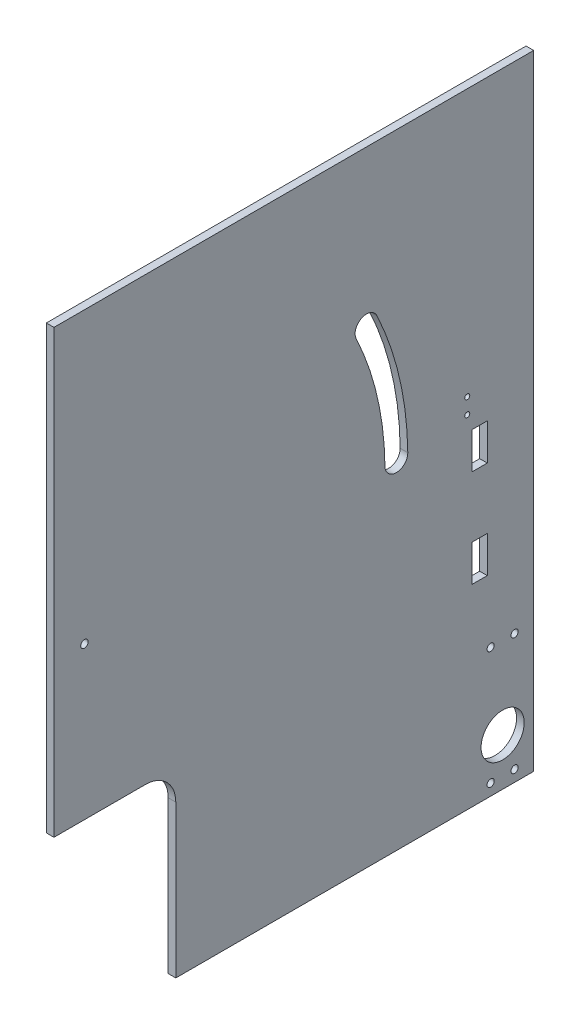
SolidWorks part; units mm, degrees
ref_plane "Front" through (0, 0, 0) normal (0, 0, 1) x (1, 0, 0)
ref_plane "Top" through (0, 0, 0) normal (0, 1, 0) x (1, 0, 0)
ref_plane "Right" through (0, 0, 0) normal (1, 0, 0) x (0, 0, -1)
sketch "Sketch1" plane through (0, 0, 0) normal (1, 0, 0) x (0, 0, -1)
  line L1 (-100.0125, 130.175) -> (100.0125, 130.175)
  line L2 (-100.0125, 130.175) -> (-100.0125, -130.175)
  line L3 (-100.0125, -130.175) -> (100.0125, -130.175)
  line L4 (100.0125, 130.175) -> (100.0125, -130.175)
  point P4 (-100.0125, 0)
  point P6 (0, 130.175)
  dimension "D1" = 260.35
  dimension "D2" = 200.025
extrude "Boss-Extrude1" add sketch "Sketch1" along normal blind 3.175
sketch "Sketch3" plane through (0, 0, 0) normal (-1, 0, 0) x (0, 0, 1)
  line L0 (-55.5625, 104.775) -> (77.7875, 104.775)
  line L1 (77.7875, 79.375) -> (-55.5625, 79.375)
  line L2 (-26.9875, 130.175) -> (-26.9875, -130.175) construction
  line L3 (-100.0125, 130.175) -> (100.0125, 130.175) construction
  line L4 (100.0125, -130.175) -> (-100.0125, -130.175) construction
  line L5 (100.0125, 130.175) -> (100.0125, -130.175) construction
  line L6 (-60.7375, 79.375) -> (-60.7375, 80.4772)
  line L12 (-55.5625, 92.075) -> (-68.2625, 92.075) construction
  arc A0 (77.7875, 104.775) -> (77.7875, 79.375) centre (77.7875, 92.075) cw
  arc A1 (-55.5625, 79.375) -> (-55.5625, 104.775) centre (-55.5625, 92.075) cw
  point P15 (90.4875, 92.075)
  dimension "D1" = 25.4
  dimension "D3" = 133.35
  dimension "D2" = 9.525
  dimension "D4" = 127
  dimension "D5" = 222.25
  dimension "D8" = 5.175
extrude "Cut-Extrude1" [suppressed] cut sketch "Sketch3" against normal through all contours A1 L1 A0 L0
sketch "Sketch6" plane through (3.175, 0, 0) normal (1, 0, 0) x (0, 0, -1)
  line L0 (117.5875, -88.265) -> (117.5875, -83.185)
  line L1 (139.5875, -83.185) -> (139.5875, -88.265)
  line L2 (111.5875, -103.765) -> (111.5875, -98.685)
  line L3 (114.5875, -103.765) -> (114.5875, -98.685)
  line L4 (111.5875, -72.765) -> (111.5875, -67.685)
  line L5 (114.5875, -72.765) -> (114.5875, -67.685)
  line L6 (128.5875, -83.185) -> (128.5875, -88.265) construction
  line L7 (145.5875, -103.765) -> (145.5875, -98.685)
  line L8 (142.5875, -103.765) -> (142.5875, -98.685)
  line L9 (142.5875, -72.765) -> (142.5875, -67.685)
  line L10 (145.5875, -72.765) -> (145.5875, -67.685)
  line L11 (-100.0125, 130.175) -> (-100.0125, -130.175) construction
  line L12 (-100.0125, -130.175) -> (100.0125, -130.175) construction
  arc A0 (117.5875, -88.265) -> (139.5875, -88.265) centre (128.5875, -88.265) ccw
  arc A1 (139.5875, -83.185) -> (117.5875, -83.185) centre (128.5875, -83.185) ccw
  arc A2 (111.5875, -103.765) -> (114.5875, -103.765) centre (113.0875, -103.765) ccw
  arc A3 (114.5875, -98.685) -> (111.5875, -98.685) centre (113.0875, -98.685) ccw
  arc A4 (111.5875, -72.765) -> (114.5875, -72.765) centre (113.0875, -72.765) ccw
  arc A5 (114.5875, -67.685) -> (111.5875, -67.685) centre (113.0875, -67.685) ccw
  arc A6 (145.5875, -103.765) -> (142.5875, -103.765) centre (144.0875, -103.765) cw
  arc A7 (142.5875, -98.685) -> (145.5875, -98.685) centre (144.0875, -98.685) cw
  arc A8 (145.5875, -72.765) -> (142.5875, -72.765) centre (144.0875, -72.765) cw
  arc A9 (142.5875, -67.685) -> (145.5875, -67.685) centre (144.0875, -67.685) cw
  circle A10 centre (113.0875, -69.36) radius 3.175
  circle A11 centre (144.0875, -69.36) radius 3.175
  circle A12 centre (113.0875, -102.09) radius 3.175
  circle A13 centre (144.0875, -102.09) radius 3.175
  point P37 (128.5875, -85.725)
  point P38 (139.5875, -85.725)
  dimension "D5" = 1.5
  dimension "D9" = 1.5
  dimension "D12" = 6.35
  dimension "D1" = 5.08
  dimension "D2" = 5.08
  dimension "D3" = 15.5
  dimension "D4" = 15.5
  dimension "D6" = 15.5
  dimension "D7" = 15.5
  dimension "D8" = 5.08
  dimension "D10" = 228.6
  dimension "D11" = 44.45
sketch "Sketch8" plane through (0, 0, 0) normal (-1, 0, 0) x (0, 0, 1)
  line L0 (100.0125, 130.175) -> (100.0125, -130.175) construction
  line L1 (100.0125, -130.175) -> (-100.0125, -130.175) construction
  line L3 (100.0125, -130.175) -> (-100.0125, -130.175) construction
  circle A0 centre (87.3125, 9.525) radius 1.55
  circle A5 centre (-72.3175, 18.925) radius 1.05
  circle A6 centre (-72.3175, 12.425) radius 1.05
  point P11 (-63.8175, 22.225)
  dimension "D1" = 3.1
  dimension "D15" = 3.3
  dimension "D8" = 2.1
  dimension "D2" = 12.7
  dimension "D3" = 139.7
  dimension "D6" = 151.13
  dimension "D7" = 152.4
  dimension "D9" = 6.5
  dimension "D12" = 8.5
extrude "Cut-Extrude7" cut sketch "Sketch8" against normal through all
sketch "Sketch9" plane through (0, 0, 0) normal (-1, 0, 0) x (0, 0, 1)
  line L0 (100.0125, 130.175) -> (100.0125, -130.175) construction
  line L1 (100.0125, -53.975) -> (49.2125, -53.975)
  line L2 (100.0125, -53.975) -> (100.0125, -130.175)
  line L3 (100.0125, -130.175) -> (49.2125, -130.175)
  line L4 (49.2125, -53.975) -> (49.2125, -130.175)
  line L5 (100.0125, -130.175) -> (-100.0125, -130.175) construction
  dimension "D1" = 50.8
  dimension "D2" = 76.2
extrude "Cut-Extrude8" cut sketch "Sketch9" against normal through all
fillet "Fillet1" radius 12.7 1 edges at (1.5875, -53.975, 49.2125)
sketch "Sketch10" plane through (0, 0, 0) normal (-1, 0, 0) x (0, 0, 1)
  line L4 (-42.8232, -130.175) -> (-42.8232, 6.325) construction
  line L5 (49.2125, -130.175) -> (-100.0125, -130.175) construction
  arc A9 (-28.2913, 69.3688) -> (-42.8232, 6.325) centre (87.3125, 9.525) ccw construction
  arc A10 (-34.6312, 67.0954) -> (-47.5281, 11.1443) centre (87.3125, 9.525) ccw
  arc A11 (-26.0179, 63.0289) -> (-38.0038, 11.03) centre (87.3125, 9.525) ccw
  arc A12 (-47.5281, 11.1443) -> (-38.0038, 11.03) centre (-42.766, 11.0872) ccw
  arc A13 (-34.6312, 67.0954) -> (-26.0179, 63.0289) centre (-30.3245, 65.0622) cw
  circle A14 centre (87.3125, 9.525) radius 125.3254 construction
  circle A15 centre (87.3125, 9.525) radius 130.175 construction
  circle A16 centre (87.3125, 9.525) radius 134.8504 construction
  point P23 (-28.2913, 69.3688)
  dimension "D1" = 4.7625
  dimension "D2" = 136.5
  dimension "D4" = 260.35
  dimension "D3" = 53.975
extrude "Cut-Extrude9" cut sketch "Sketch10" against normal through all
sketch "Sketch14" plane through (3.175, 0, 0) normal (1, 0, 0) x (0, 0, -1)
  line L0 (36.5125, -130.175) -> (36.5125, 130.175) construction
  line L5 (-49.2125, -130.175) -> (100.0125, -130.175) construction
  line L6 (100.0125, 130.175) -> (-100.0125, 130.175) construction
  line L7 (-100.0125, 130.175) -> (-100.0125, -53.975) construction
  line L14 (65.0875, -120.523) -> (65.0875, -126.873) construction
  circle A0 centre (-87.3125, 9.525) radius 181.0945 construction
  arc A1 (28.4957, -127.7406) -> (34.7793, -121.5542) centre (28.4314, -121.3909) ccw construction
  circle A2 centre (65.0875, -126.873) radius 1.5
  circle A3 centre (65.0875, -120.523) radius 1.5
  dimension "D6" = 3
  dimension "D7" = 6.35
  dimension "D1" = 136.525
  dimension "D8" = 3.302
  dimension "D9" = 28.575
extrude "Cut-Extrude11" [suppressed] cut sketch "Sketch14" against normal through all
sketch "Sketch15" plane through (3.175, 0, 0) normal (1, 0, 0) x (0, 0, -1)
  line L1 (74.3175, 6.075) -> (80.6675, 6.075)
  line L2 (74.3175, 6.075) -> (74.3175, -9.165)
  line L3 (74.3175, -9.165) -> (80.6675, -9.165)
  line L4 (80.6675, 6.075) -> (80.6675, -9.165)
  line L11 (74.3175, -34.565) -> (80.6675, -34.565)
  line L12 (74.3175, -34.565) -> (74.3175, -49.805)
  line L13 (74.3175, -49.805) -> (80.6675, -49.805)
  line L14 (80.6675, -34.565) -> (80.6675, -49.805)
  circle A0 centre (72.3175, 12.425) radius 1.05 construction
  dimension "D4" = 2
  dimension "D1" = 6.35
  dimension "D2" = 15.24
  dimension "D3" = 25.4
  dimension "D5" = 6.35
extrude "Cut-Extrude12" cut sketch "Sketch15" against normal through all
sketch "Sketch16" plane through (3.175, 0, 0) normal (1, 0, 0) x (0, 0, -1)
  line L0 (82.075, -76.4125) -> (92.075, -76.4125) construction
  line L1 (82.075, -76.4125) -> (82.075, -125.4125) construction
  line L2 (92.075, -76.4125) -> (92.075, -125.4125) construction
  line L3 (82.075, -125.4125) -> (92.075, -125.4125) construction
  line L4 (100.0125, -130.175) -> (100.0125, 130.175) construction
  line L6 (87.075, -125.4125) -> (87.075, -110.5625) construction
  line L7 (87.075, -119.5625) -> (68.66, -119.5625) construction
  line L9 (-49.2125, -130.175) -> (100.0125, -130.175) construction
  circle A0 centre (82.075, -125.4125) radius 1.5
  circle A1 centre (82.075, -76.4125) radius 1.5
  circle A2 centre (92.075, -125.4125) radius 1.5
  circle A3 centre (92.075, -76.4125) radius 1.5
  circle A4 centre (87.075, -110.5625) radius 9
  dimension "D1" = 3
  dimension "D7" = 18
  dimension "D2" = 10
  dimension "D3" = 49
  dimension "D4" = 14.85
  dimension "D5" = 7.9375
  dimension "D6" = 4.7625
extrude "Cut-Extrude13" cut sketch "Sketch16" against normal through all
equation "\"bottomThickness\"= .220in"
equation "\"wallThickness\"= .125in"
equation "\"D1@Boss-Extrude1\"=\"wallThickness\""
